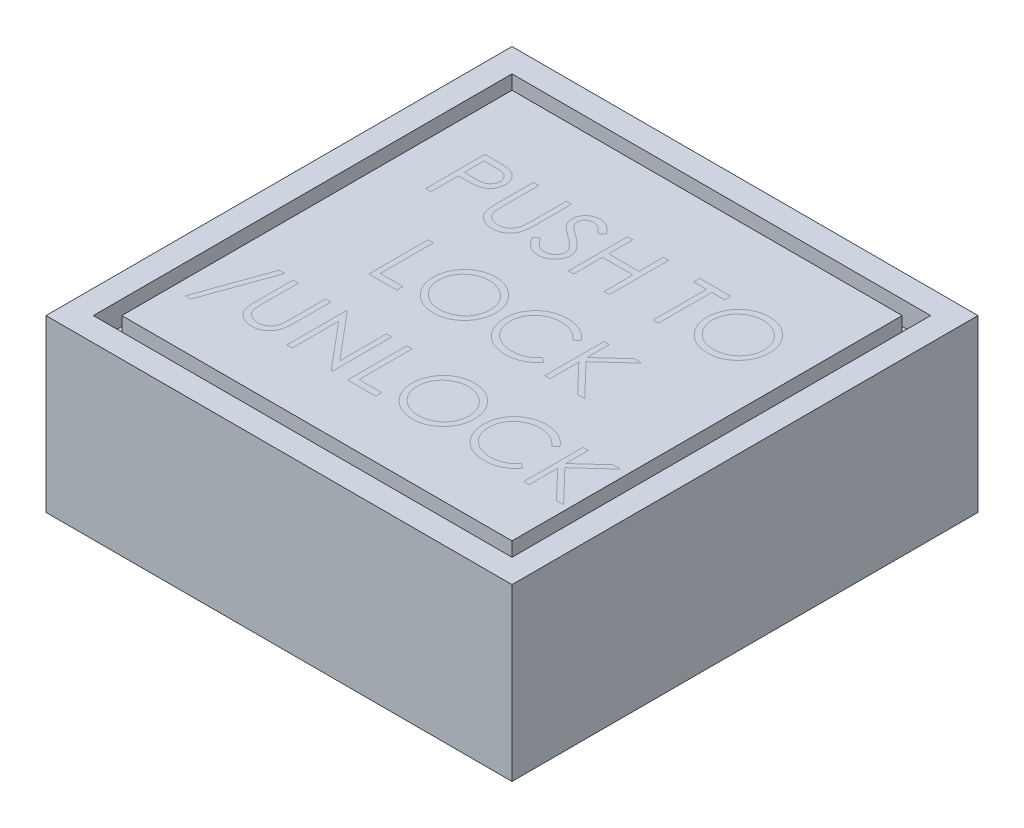
SolidWorks part; units mm, degrees
material "Stainless Steel (ferritic)"
ref_plane "Front Plane" through (0, 0, 0) normal (0, 0, 1) x (1, 0, 0)
ref_plane "Back of Button Plane" through (0, 0, 0) normal (0, 1, 0) x (1, 0, 0)
ref_plane "Right Plane" through (0, 0, 0) normal (1, 0, 0) x (0, 0, -1)
sketch "Sketch1" plane through (0, 0, 0) normal (0, 1, 0) x (1, 0, 0)
  line L1 (0, 0) -> (124.968, 0)
  line L2 (0, 0) -> (0, 124.968)
  line L3 (0, 124.968) -> (124.968, 124.968)
  line L4 (124.968, 0) -> (124.968, 124.968)
  dimension "D1" = 124.968
  dimension "D2" = 124.968
extrude "Boss-Extrude1" add sketch "Sketch1" along normal blind 45.72
sketch "Sketch4" plane through (0, 45.72, 0) normal (0, 1, 0) x (1, 0, 0)
  line L8 (6.35, 118.618) -> (6.35, 6.35)
  line L9 (6.35, 6.35) -> (118.618, 6.35)
  line L10 (118.618, 6.35) -> (118.618, 118.618)
  line L11 (118.618, 118.618) -> (6.35, 118.618)
  line L12 (6.35, 118.618) -> (6.35, 6.35)
  line L13 (6.35, 6.35) -> (118.618, 6.35)
  line L14 (118.618, 6.35) -> (118.618, 118.618)
  line L15 (118.618, 118.618) -> (6.35, 118.618)
  dimension "D1" = 6.35
extrude "Cut-Extrude1" cut sketch "Sketch4" against normal blind 6.35
sketch "Sketch6" plane through (0, 39.37, 0) normal (0, 1, 0) x (1, 0, 0)
  line L8 (114.808, 10.16) -> (114.808, 114.808)
  line L9 (10.16, 10.16) -> (114.808, 10.16)
  line L10 (10.16, 114.808) -> (10.16, 10.16)
  line L11 (114.808, 114.808) -> (10.16, 114.808)
  line L12 (114.808, 10.16) -> (114.808, 114.808)
  line L13 (10.16, 10.16) -> (114.808, 10.16)
  line L14 (10.16, 114.808) -> (10.16, 10.16)
  line L15 (114.808, 114.808) -> (10.16, 114.808)
  dimension "D1" = 3.81
extrude "Boss-Extrude2" add sketch "Sketch6" along normal blind 6.35
sketch "Sketch11" plane through (0, 45.72, 0) normal (0, 1, 0) x (1, 0, 0)
  text T0 " PUSH TO \r\n   LOCK\r\n/UNLOCK" font "Century Gothic" height in points 60
wrap "Wrap1" sketch "Sketch11" wrap type scribe source sketch "Sketch11" face at (62.484, 45.72, -62.484)
